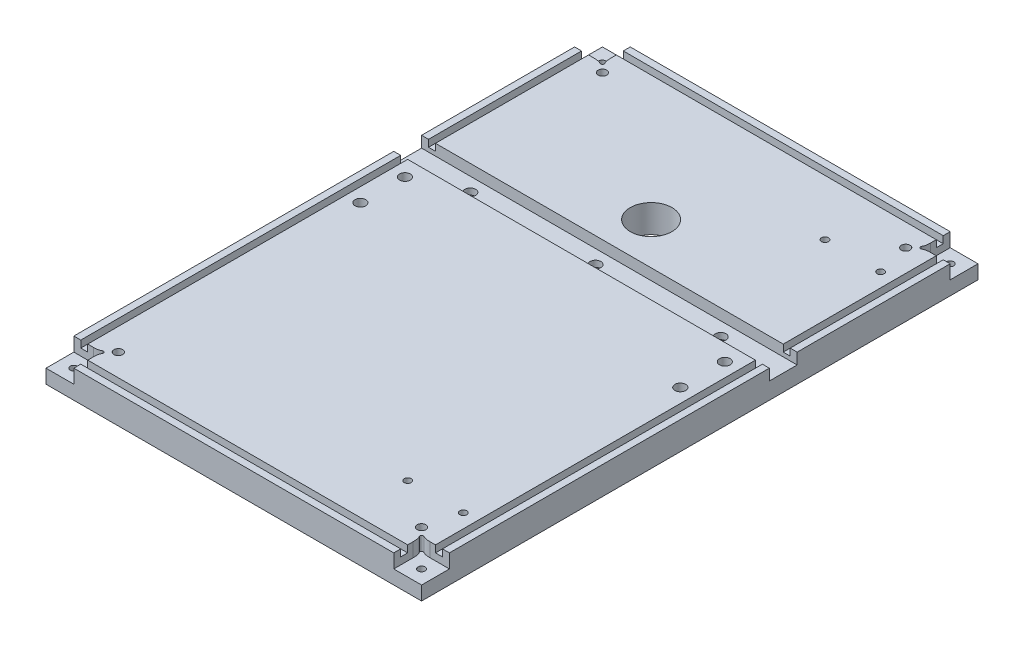
SolidWorks part; units mm, degrees
ref_plane "Front Plane" through (0, 0, 0) normal (0, 0, 1) x (1, 0, 0)
ref_plane "Top Plane" through (0, 0, 0) normal (0, 1, 0) x (1, 0, 0)
ref_plane "Right Plane" through (0, 0, 0) normal (1, 0, 0) x (0, 0, -1)
sketch "Base" plane through (0, 0, 0) normal (0, 1, 0) x (1, 0, 0)
  line L1 (-201.9764, 133.7508) -> (140.9236, 133.7508)
  line L2 (-201.9764, 133.7508) -> (-201.9764, -374.2492)
  line L3 (-201.9764, -374.2492) -> (140.9236, -374.2492)
  line L4 (140.9236, 133.7508) -> (140.9236, -374.2492)
  dimension "D1" = 342.9
  dimension "D2" = 508
extrude "Boss-Extrude1" add sketch "Base" along normal blind 25.4
sketch "Sketch2" plane through (0, 25.4, 0) normal (0, 1, 0) x (1, 0, 0)
  line L1 (172.6736, -31.3492) -> (-233.7264, -31.3492)
  line L2 (172.6736, -31.3492) -> (172.6736, -56.7492)
  line L3 (172.6736, -56.7492) -> (-233.7264, -56.7492)
  line L4 (-233.7264, -31.3492) -> (-233.7264, -56.7492)
  line L6 (140.9236, 133.7508) -> (-201.9764, 133.7508) construction
  line L9 (-30.5264, 133.7508) -> (-30.5264, -374.2492) construction
  line L10 (-201.9764, -374.2492) -> (140.9236, -374.2492) construction
  point P6 (-30.5264, -31.3492)
  dimension "D1" = 317.5
  dimension "D2" = 25.4
  dimension "D3" = 406.4
extrude "Cut-Extrude1" cut sketch "Sketch2" against normal blind 10.16
hole_wizard "CBORE for 3/8 Socket Head Cap Screw4" positions "3DSketch1" profile "Sketch3" counterbore size "3/8" standard "ANSI Inch" end condition up to next
sketch3d "3DSketch1"
  line L3 (-201.9764, 0, -133.7508) -> (-201.9764, 0, 374.2492) construction
  point P0 (83.7736, 0, 44.0492)
  point P2 (-30.5264, 0, 44.0492)
  point P4 (-144.8264, 0, 44.0492)
  dimension "D1" = 12.7
  dimension "D2" = 12.7
  dimension "D3" = 12.7
  dimension "D4" = 171.45
  dimension "D5" = 114.3
  dimension "D6" = 114.3
sketch "Sketch3" plane through (83.7736, 0, 44.0492) normal (1, 0, 0) x (0, 0, -1)
  line L0 (0, 0) -> (0, 15.24)
  line L1 (0, 15.24) -> (4.9022, 15.24)
  line L3 (4.9022, 15.24) -> (4.9022, 9.525)
  line L4 (4.9022, 9.525) -> (7.9375, 9.525)
  line L5 (7.9375, 9.525) -> (7.9375, 0)
  line L7 (7.9375, 0) -> (0, 0)
  line L11 (0, -6.35) -> (0, 107.95) construction
  dimension "Thru Hole Dia." = 9.8044
  dimension "Thru Hole Depth" = 15.24
  dimension "C'Bore Dia." = 15.875
  dimension "C'Bore Depth" = 9.525
hole_wizard "CBORE for 3/8 Socket Head Cap Screw3" positions "Sketch4" profile "Sketch6" counterbore size "3/8" standard "ANSI Inch" end condition up to next
sketch "Sketch4" plane through (0, 0, 0) normal (0, -1, 0) x (-1, 0, 0)
  line L0 (201.9764, -56.7492) -> (-140.9236, -56.7492) construction
  line L1 (-140.9236, -374.2492) -> (-140.9236, 133.7508) construction
  line L3 (201.9764, 133.7508) -> (201.9764, -374.2492) construction
  point P0 (-115.5236, -71.9892)
  point P2 (-115.5236, -112.6292)
  point P4 (176.5764, -71.9892)
  point P6 (176.5764, -112.6292)
  dimension "D1" = 15.24
  dimension "D2" = 25.4
  dimension "D3" = 25.4
  dimension "D4" = 40.64
  dimension "D5" = 15.24
  dimension "D6" = 25.4
  dimension "D7" = 40.64
  dimension "D8" = 25.4
sketch "Sketch6" plane through (115.5236, 0, 71.9892) normal (1, 0, 0) x (0, 0, -1)
  line L0 (0, 0) -> (0, 25.4)
  line L1 (0, 25.4) -> (4.9022, 25.4)
  line L3 (4.9022, 25.4) -> (4.9022, 15.24)
  line L4 (4.9022, 15.24) -> (7.9375, 15.24)
  line L5 (7.9375, 15.24) -> (7.9375, 0)
  line L7 (7.9375, 0) -> (0, 0)
  line L11 (0, -6.35) -> (0, 107.95) construction
  dimension "Thru Hole Dia." = 9.8044
  dimension "Thru Hole Depth" = 25.4
  dimension "C'Bore Dia." = 15.875
  dimension "C'Bore Depth" = 15.24
hole_wizard "CBORE for 1/4 Socket Head Cap Screw1" positions "3DSketch2" profile "Sketch9" counterbore size "1/4" standard "ANSI Inch" end condition up to next
sketch3d "3DSketch2"
  line L0 (140.9236, 0, -133.7508) -> (-201.9764, 0, -133.7508) construction
  line L1 (140.9236, 0, 374.2492) -> (140.9236, 0, -133.7508) construction
  line L2 (-201.9764, 0, -133.7508) -> (-201.9764, 0, 374.2492) construction
  line L3 (-201.9764, 0, 374.2492) -> (140.9236, 0, 374.2492) construction
  point P0 (128.2236, 0, 361.5492)
  point P2 (-189.2764, 0, 361.5492)
  point P4 (-189.2764, 0, -121.0508)
  point P6 (128.2236, 0, -121.0508)
  dimension "D1" = 12.7
  dimension "D2" = 12.7
  dimension "D3" = 12.7
  dimension "D4" = 12.7
  dimension "D5" = 12.7
  dimension "D6" = 12.7
  dimension "D7" = 12.7
  dimension "D8" = 12.7
sketch "Sketch9" plane through (128.2236, 0, 361.5492) normal (1, 0, 0) x (0, 0, -1)
  line L0 (0, 0) -> (0, 25.4)
  line L1 (0, 25.4) -> (3.2639, 25.4)
  line L3 (3.2639, 25.4) -> (3.2639, 6.35)
  line L4 (3.2639, 6.35) -> (5.5562, 6.35)
  line L5 (5.5562, 6.35) -> (5.5562, 0)
  line L7 (5.5562, 0) -> (0, 0)
  line L11 (0, -6.35) -> (0, 107.95) construction
  dimension "Thru Hole Dia." = 6.5278
  dimension "Thru Hole Depth" = 25.4
  dimension "C'Bore Dia." = 11.1125
  dimension "C'Bore Depth" = 6.35
sketch "Sketch8" plane through (0, 25.4, 0) normal (0, 1, 0) x (1, 0, 0)
  line L0 (116.3173, -347.4744) -> (115.5236, -348.8492) construction
  line L1 (140.9236, -374.2492) -> (115.5236, -374.2492)
  line L2 (140.9236, -374.2492) -> (140.9236, -348.8492)
  line L3 (140.9236, -348.8492) -> (123.1436, -348.8492)
  line L4 (115.5236, -374.2492) -> (115.5236, -356.4692)
  line L5 (-201.9764, -374.2492) -> (-176.5764, -374.2492)
  line L6 (-201.9764, -374.2492) -> (-201.9764, -348.8492)
  line L7 (-201.9764, -348.8492) -> (-184.1964, -348.8492)
  line L8 (-176.5764, -374.2492) -> (-176.5764, -356.4692)
  line L9 (-201.9764, 133.7508) -> (-176.5764, 133.7508)
  line L10 (-201.9764, 133.7508) -> (-201.9764, 108.3508)
  line L11 (-201.9764, 108.3508) -> (-184.1964, 108.3508)
  line L12 (-176.5764, 133.7508) -> (-176.5764, 115.9708)
  line L13 (140.9236, 133.7508) -> (115.5236, 133.7508)
  line L14 (140.9236, 133.7508) -> (140.9236, 108.3508)
  line L15 (140.9236, 108.3508) -> (123.1436, 108.3508)
  line L16 (115.5236, 133.7508) -> (115.5236, 115.9708)
  line L17 (115.5236, -348.8492) -> (123.1436, -348.8492) construction
  line L18 (115.5236, -356.4692) -> (115.5236, -348.8492) construction
  line L19 (115.5236, -348.8492) -> (114.1488, -349.6429) construction
  line L20 (115.5236, 108.3508) -> (116.3173, 106.976) construction
  line L21 (115.5236, 108.3508) -> (114.1488, 109.1446) construction
  line L22 (-176.5764, 108.3508) -> (-175.2016, 109.1446) construction
  line L23 (-176.5764, 108.3508) -> (-177.3702, 106.976) construction
  line L24 (-176.5764, -348.8492) -> (-175.2016, -349.6429) construction
  line L25 (-176.5764, -348.8492) -> (-177.3702, -347.4744) construction
  arc A0 (116.3173, -347.4744) -> (114.1488, -349.6429) centre (115.5236, -348.8492) ccw
  arc A1 (114.1488, 109.1446) -> (116.3173, 106.976) centre (115.5236, 108.3508) ccw
  arc A2 (-177.3702, 106.976) -> (-175.2016, 109.1446) centre (-176.5764, 108.3508) ccw
  arc A3 (-175.2016, -349.6429) -> (-177.3702, -347.4744) centre (-176.5764, -348.8492) ccw
  spline S0 degree 3 poles (123.1436, -348.8492) (120.8225, -348.8492) (118.3275, -348.6349) (116.3173, -347.4744) knots 0 0 0 0 1 1 1 1
  spline S1 degree 3 poles (115.5236, -356.4692) (115.5236, -353.9168) (115.3093, -351.6531) (114.1488, -349.6429) knots 0 0 0 0 1 1 1 1
  spline S2 degree 3 poles (123.1436, 108.3508) (120.8225, 108.3508) (118.3275, 108.1366) (116.3173, 106.976) knots 0 0 0 0 1 1 1 1
  spline S3 degree 3 poles (114.1488, 109.1446) (115.3093, 111.1547) (115.5236, 113.6497) (115.5236, 115.9708) knots 0 0 0 0 1 1 1 1
  spline S4 degree 3 poles (-176.5764, 115.9708) (-176.5764, 113.4184) (-176.3621, 111.1547) (-175.2016, 109.1446) knots 0 0 0 0 1 1 1 1
  spline S5 degree 3 poles (-177.3702, 106.976) (-179.3803, 108.1366) (-181.8753, 108.3508) (-184.1964, 108.3508) knots 0 0 0 0 1 1 1 1
  spline S6 degree 3 poles (-175.2016, -349.6429) (-176.7942, -352.4013) (-176.5764, -354.9687) (-176.5764, -356.4692) knots 0 0 0 0 1 1 1 1
  spline S7 degree 3 poles (-177.3702, -347.4744) (-180.1285, -349.0669) (-182.696, -348.8492) (-184.1964, -348.8492) knots 0 0 0 0 1 1 1 1
  point P23 (117.1111, -348.8492)
  point P27 (115.5236, -350.4367)
  dimension "D9" = 7.62
  dimension "D10" = 1.5875
  dimension "D15" = 60
  dimension "D16" = 1.5875
  dimension "D20" = 3.175
  dimension "D25" = 60
  dimension "D28" = 3.175
  dimension "D2" = 25.4
  dimension "D3" = 25.4
  dimension "D4" = 25.4
  dimension "D5" = 25.4
  dimension "D6" = 25.4
  dimension "D7" = 25.4
  dimension "D8" = 25.4
  dimension "D11" = 7.62
  dimension "D12" = 25.4
  dimension "D13" = 60
  dimension "D14" = 60
  dimension "D17" = 60
  dimension "D18" = 7.62
  dimension "D19" = 7.62
  dimension "D21" = 60
  dimension "D22" = 60
  dimension "D23" = 7.62
  dimension "D24" = 7.62
  dimension "D26" = 60
  dimension "D27" = 7.62
  dimension "D29" = 7.62
extrude "Cut-Extrude3" cut sketch "Sketch8" against normal blind 12.7
sketch "Sketch10" plane through (0, 25.4, 0) normal (0, 1, 0) x (1, 0, 0)
  line L1 (128.2236, 108.3508) -> (134.5736, 108.3508)
  line L2 (128.2236, 108.3508) -> (128.2236, -348.8492)
  line L3 (128.2236, -348.8492) -> (134.5736, -348.8492)
  line L4 (134.5736, 108.3508) -> (134.5736, -348.8492)
  line L5 (140.9236, -348.8492) -> (140.9236, -56.7492) construction
  line L8 (-201.9764, 108.3508) -> (-201.9764, -31.3492) construction
  line L9 (-195.6264, 108.3508) -> (-189.2764, 108.3508)
  line L10 (-195.6264, 108.3508) -> (-195.6264, -348.8492)
  line L11 (-195.6264, -348.8492) -> (-189.2764, -348.8492)
  line L12 (-189.2764, 108.3508) -> (-189.2764, -348.8492)
  line L13 (-184.1964, -348.8492) -> (-201.9764, -348.8492) construction
  line L14 (-201.9764, 108.3508) -> (-184.1964, 108.3508) construction
  line L15 (123.1436, 108.3508) -> (140.9236, 108.3508) construction
  line L16 (140.9236, -348.8492) -> (123.1436, -348.8492) construction
  line L17 (-176.5764, 115.9708) -> (-176.5764, 133.7508) construction
  line L18 (-176.5764, 127.4008) -> (115.5236, 127.4008)
  line L19 (-176.5764, 127.4008) -> (-176.5764, 121.0508)
  line L20 (-176.5764, 121.0508) -> (115.5236, 121.0508)
  line L21 (115.5236, 127.4008) -> (115.5236, 121.0508)
  line L22 (115.5236, 133.7508) -> (115.5236, 115.9708) construction
  line L23 (115.5236, 133.7508) -> (-176.5764, 133.7508) construction
  line L24 (-176.5764, -374.2492) -> (-176.5764, -356.4692) construction
  line L25 (-176.5764, -361.5492) -> (115.5236, -361.5492)
  line L26 (-176.5764, -361.5492) -> (-176.5764, -367.8992)
  line L27 (-176.5764, -367.8992) -> (115.5236, -367.8992)
  line L28 (115.5236, -361.5492) -> (115.5236, -367.8992)
  line L29 (115.5236, -356.4692) -> (115.5236, -374.2492) construction
  line L30 (-176.5764, -374.2492) -> (115.5236, -374.2492) construction
  dimension "D1" = 6.35
  dimension "D2" = 6.35
  dimension "D3" = 6.35
  dimension "D4" = 6.35
  dimension "D5" = 6.35
  dimension "D6" = 6.35
  dimension "D7" = 6.35
  dimension "D8" = 6.35
extrude "Cut-Extrude4" cut sketch "Sketch10" against normal blind 6.35
hole_wizard "3/8-16 Tapped Hole2" positions "Sketch17" profile "Sketch18" tap size "3/8-16" standard "ANSI Inch" end condition up to next
sketch "Sketch17" plane through (0, 0, 0) normal (0, -1, 0) x (-1, 0, 0)
  line L0 (-140.9236, 133.7508) -> (201.9764, 133.7508) construction
  line L1 (-140.9236, -374.2492) -> (-140.9236, 133.7508) construction
  line L2 (201.9764, 133.7508) -> (201.9764, -374.2492) construction
  line L3 (201.9764, -374.2492) -> (-140.9236, -374.2492) construction
  point P0 (-107.9036, -341.2292)
  point P2 (168.9564, -341.2292)
  point P4 (168.9564, 100.7308)
  point P6 (-107.9036, 100.7308)
  dimension "D1" = 33.02
  dimension "D2" = 33.02
  dimension "D3" = 33.02
  dimension "D4" = 33.02
  dimension "D5" = 33.02
  dimension "D6" = 33.02
  dimension "D7" = 33.02
  dimension "D8" = 33.02
sketch "Sketch18" plane through (107.9036, 0, 341.2292) normal (1, 0, 0) x (0, 0, -1)
  line L0 (0, 0) -> (0, 25.4)
  line L1 (0, 25.4) -> (3.9687, 25.4)
  line L2 (3.9687, 25.4) -> (3.9687, 0)
  line L5 (3.9687, 0) -> (0, 0)
  line L11 (0, -6.35) -> (0, 107.95) construction
  dimension "Thru Tap Drill Dia." = 7.9375
  dimension "Thru Tap Drill Depth" = 25.4
cosmetic thread "Hole Thread5" parameters "D2"=9.525
cosmetic thread "Hole Thread6" parameters "D2"=9.525
cosmetic thread "Hole Thread7" parameters "D2"=9.525
cosmetic thread "Hole Thread8" parameters "D2"=9.525
sketch "Sketch19" plane through (0, 0, 0) normal (0, -1, 0) x (1, 0, 0)
  circle A0 centre (-168.9564, -100.7308) radius 9.525
  circle A1 centre (-168.9564, 341.2292) radius 9.525
  circle A2 centre (107.9036, 341.2292) radius 9.525
  circle A3 centre (108.2173, -100.7308) radius 9.525
  dimension "D1" = 19.05
  dimension "D2" = 19.05
  dimension "D3" = 19.05
  dimension "D4" = 19.05
extrude "Cut-Extrude5" cut sketch "Sketch19" against normal blind 1.27
ref_plane "Plane1" through (0, 0, 120.2492) normal (0, 0, 1) x (1, 0, 0)
sketch "Sketch20" plane through (0, 0, 0) normal (0, -1, 0) x (1, 0, 0)
  line L0 (-30.5264, -133.7508) -> (-30.5264, 374.2492) construction
  line L1 (140.9236, -133.7508) -> (-201.9764, -133.7508) construction
  line L2 (-201.9764, 374.2492) -> (140.9236, 374.2492) construction
  line L3 (128.2236, 31.3492) -> (-189.2764, 31.3492) construction
  circle A0 centre (115.5236, 310.7492) radius 3.175 construction
  circle A1 centre (64.7236, 310.7492) radius 3.175 construction
  circle A2 centre (115.5236, 310.7492) radius 3.175
  circle A3 centre (64.7236, 310.7492) radius 3.175
  circle A4 centre (64.7236, -70.2508) radius 3.175 construction
  circle A5 centre (115.5236, -70.2508) radius 3.175 construction
  circle A6 centre (64.7236, -70.2508) radius 3.175
  circle A7 centre (115.5236, -70.2508) radius 3.175
  circle A8 centre (-30.5264, -6.7508) radius 19.05
  point P20 (0, 0)
  dimension "D1" = 38.1
  dimension "D2" = 38.1
extrude "Cut-Extrude6" cut sketch "Sketch20" against normal through all
